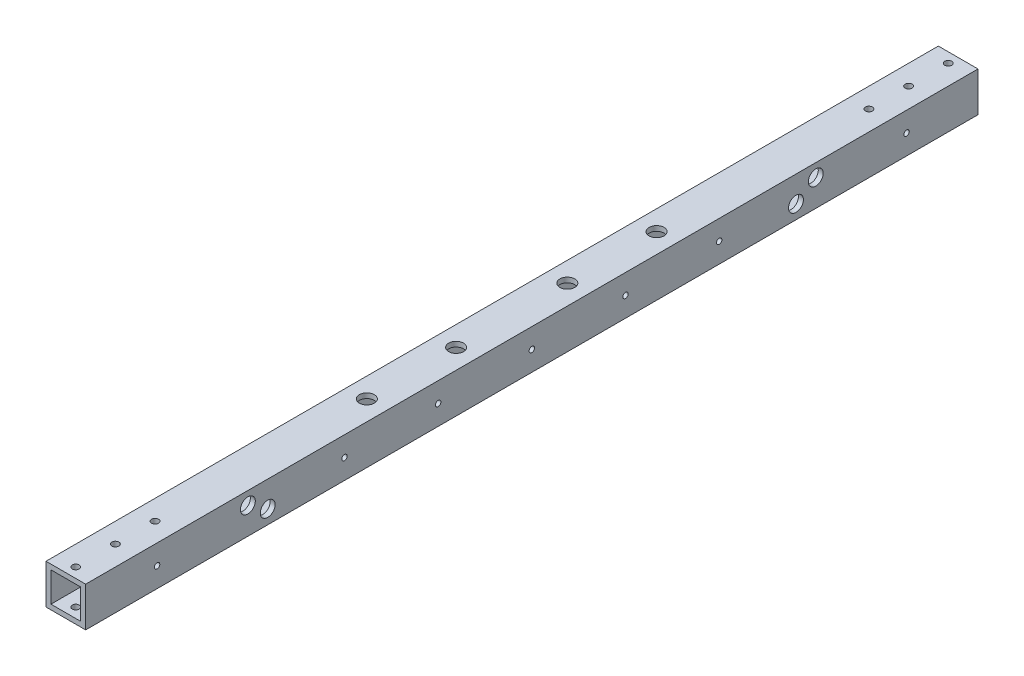
SolidWorks part; units mm, degrees
material "6061-T6 (SS)"
ref_plane "Front Plane" through (0, 0, 0) normal (0, 0, 1) x (1, 0, 0)
ref_plane "Top Plane" through (0, 0, 0) normal (0, 1, 0) x (1, 0, 0)
ref_plane "Right Plane" through (0, 0, 0) normal (1, 0, 0) x (0, 0, -1)
sketch "Sketch1" plane through (0, 0, 0) normal (0, 0, 1) x (1, 0, 0)
  line L1 (-12.7, -12.7) -> (12.7, -12.7)
  line L2 (-12.7, -12.7) -> (-12.7, 12.7)
  line L3 (-12.7, 12.7) -> (12.7, 12.7)
  line L4 (12.7, -12.7) -> (12.7, 12.7)
  line L5 (-12.7, -12.7) -> (12.7, 12.7) construction
  line L6 (-12.7, 12.7) -> (12.7, -12.7) construction
  point P0 (0, 0)
  dimension "D1" = 25.4
  dimension "D2" = 25.4
extrude "Extrude-Thin1" add sketch "Sketch1" along normal blind 571.5 thin thin type one direction reverse wall 3.175
hole_wizard "#8 Clearance Hole1" positions "3DSketch1" profile "Sketch3" hole size "#8" standard "ANSI Inch" end condition through all
sketch3d "3DSketch1"
  line L1 (12.7, 12.7, 0) -> (-12.7, 12.7, 0) construction
  line L6 (0, 12.7, 571.5) -> (0, 12.7, 0) construction
  line L7 (12.7, 12.7, 571.5) -> (-12.7, 12.7, 571.5) construction
  point P57 (0, 12.7, 6.35)
  point P59 (0, 12.7, 31.75)
  point P61 (0, 12.7, 57.15)
  point P63 (0, 12.7, 539.75)
  point P65 (0, 12.7, 514.35)
  point P67 (0, 12.7, 565.15)
  dimension "D1" = 25.4
  dimension "D2" = 25.4
  dimension "D3" = 6.35
  dimension "D4" = 25.4
  dimension "D5" = 25.4
  dimension "D6" = 6.35
sketch "Sketch3" plane through (0, 12.7, 565.15) normal (1, 0, 0) x (0, 0, 1)
  line L0 (0, 0) -> (0, 25.4)
  line L1 (0, 25.4) -> (2.2479, 25.4)
  line L2 (2.2479, 25.4) -> (2.2479, 0)
  line L5 (2.2479, 0) -> (0, 0)
  line L11 (0, -6.35) -> (0, 107.95) construction
  dimension "Thru Hole Dia." = 4.4958
  dimension "Thru Hole Depth" = 25.4
hole_wizard "#8-32 Tapped Hole1" positions "Sketch8" profile "Sketch9" tap size "#8-32" standard "ANSI Inch"
sketch "Sketch8" plane through (12.7, -82.55, 285.75) normal (1, 0, 0) x (0, 0, -1)
  point P0 (-240, 82.55)
  point P6 (-120, 82.55)
  point P9 (-60, 82.55)
  point P12 (0, 82.55)
  point P15 (60, 82.55)
  point P18 (120, 82.55)
  point P24 (240, 82.55)
sketch "Sketch9" plane through (12.7, 0, 525.75) normal (0, 1, 0) x (0, 0, -1)
  line L0 (0, 0) -> (0, 13.3314)
  line L1 (0, 13.3314) -> (1.7272, 12.2936)
  line L2 (1.7272, 12.2936) -> (1.7272, 0)
  line L3 (1.7272, 0) -> (0, 0)
  line L4 (0, 13.3314) -> (-1.7272, 12.2936) construction
  line L5 (0, -6.35) -> (0, 107.95) construction
  dimension "Tap Drill Dia." = 3.4544
  dimension "Tap Drill Depth" = 12.2936
  dimension "Drill Angle" = 118
hole_wizard "3/8 (0.375) Diameter Hole2" positions "Sketch12" profile "Sketch13" hole size "3/8" standard "ANSI Inch" end condition through all
sketch "Sketch12" plane through (-12.7, -82.55, 285.75) normal (1, 0, 0) x (0, 0, -1)
  point P0 (-181.864, 86.995)
  point P3 (-169.164, 78.74)
  point P6 (169.164, 78.74)
  point P9 (181.864, 86.995)
  point P12 (181.864, 57.15)
  point P15 (-181.864, 57.15)
sketch "Sketch13" plane through (-12.7, 4.445, 467.614) normal (0, 1, 0) x (0, 0, 1)
  line L0 (0, 0) -> (0, 25.4)
  line L1 (0, 25.4) -> (4.7625, 25.4)
  line L2 (4.7625, 25.4) -> (4.7625, 0)
  line L3 (4.7625, 0) -> (0, 0)
  line L4 (0, -6.35) -> (0, 107.95) construction
  dimension "Thru Hole Dia." = 9.525
  dimension "Thru Hole Depth" = 25.4
hole_wizard "3/8 (0.375) Diameter Hole3" positions "Sketch14" profile "Sketch15" hole size "3/8" standard "ANSI Inch" end condition through all
sketch "Sketch14" plane through (-346.075, 12.7, 285.75) normal (0, 1, 0) x (0, 0, 1)
  point P9 (-92.583, 346.075)
  point P12 (-35.433, 346.075)
  point P18 (35.814, 346.075)
  point P21 (92.964, 346.075)
  point P24 (-19.05, -346.775)
  point P27 (53.975, -346.775)
  point P30 (127, -346.775)
  point P42 (-381, -114.3)
  point P45 (-381, -130.175)
  point P48 (-381, -146.05)
  point P55 (-381, 114.3)
  point P58 (-381, 98.425)
  point P61 (-381, 82.55)
sketch "Sketch15" plane through (0, 12.7, 193.167) normal (1, 0, 0) x (0, 0, 1)
  line L0 (0, 0) -> (0, 25.4)
  line L1 (0, 25.4) -> (4.7625, 25.4)
  line L2 (4.7625, 25.4) -> (4.7625, 0)
  line L3 (4.7625, 0) -> (0, 0)
  line L4 (0, -6.35) -> (0, 107.95) construction
  dimension "Thru Hole Dia." = 9.525
  dimension "Thru Hole Depth" = 25.4
